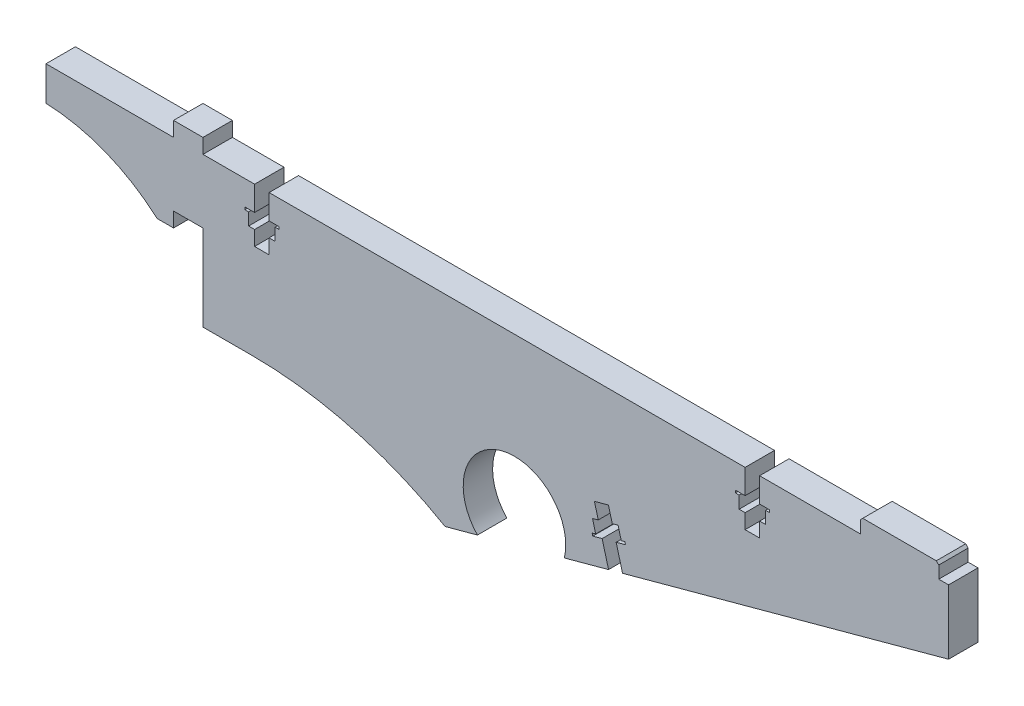
SolidWorks part; units mm, degrees
material "Oak"
ref_plane "Front Plane" through (0, 0, 0) normal (0, 0, 1) x (1, 0, 0)
ref_plane "Top Plane" through (0, 0, 0) normal (0, 1, 0) x (1, 0, 0)
ref_plane "Right Plane" through (0, 0, 0) normal (1, 0, 0) x (0, 0, -1)
sketch "Sketch1" plane through (0, 0, 0) normal (0, 0, 1) x (1, 0, 0)
  line L0 (127.02, 20) -> (127.02, 15)
  line L1 (16.5, -10.5) -> (16.5, 7)
  line L2 (16.5, 7) -> (10.5, 7)
  line L3 (10.5, 7) -> (10.5, 4)
  line L4 (10.5, 4) -> (7.1752, 4)
  line L5 (-15.5, 13) -> (-15.5, 20)
  line L6 (-15.5, 20) -> (10.5, 20)
  line L7 (166.5, 23) -> (166.5, 20)
  line L8 (72.4558, -19.231) -> (90.1661, -14.4192) construction
  line L9 (127.02, 15) -> (125.05, 15)
  line L10 (-18, 24.8801) -> (-18, -27.1715) construction
  line L11 (10.5, 20) -> (10.5, 23)
  line L12 (10.5, 23) -> (16.5, 23)
  line L13 (125.05, 15) -> (125.05, 14.5)
  line L14 (125.05, 14.5) -> (125.8, 14.5)
  line L15 (125.8, 14.5) -> (125.8, 12)
  line L16 (125.8, 12) -> (127.02, 12)
  line L17 (127.02, 12) -> (127.02, 9)
  line L18 (127.02, 9) -> (129.98, 9)
  line L19 (129.98, 12) -> (129.98, 9)
  line L20 (131.2, 12) -> (129.98, 12)
  line L21 (131.2, 14.5) -> (131.2, 12)
  line L22 (131.95, 14.5) -> (131.2, 14.5)
  line L23 (131.95, 15) -> (131.95, 14.5)
  line L24 (129.98, 15) -> (131.95, 15)
  line L25 (129.98, 20) -> (129.98, 15)
  line L26 (128.5, 20) -> (128.5, 9) construction
  line L27 (90.1661, -14.4192) -> (168.5, 6.8638)
  line L28 (80, -12) -> (81.311, -16.8251) construction
  line L29 (16.5, -10.5) -> (26.5, -10.5)
  line L30 (28.5, 20) -> (28.5, 9) construction
  line L31 (27.02, 20) -> (27.02, 15)
  line L32 (27.02, 15) -> (25.05, 15)
  line L33 (25.05, 15) -> (25.05, 14.5)
  line L34 (25.05, 14.5) -> (25.8, 14.5)
  line L35 (25.8, 14.5) -> (25.8, 12)
  line L36 (25.8, 12) -> (27.02, 12)
  line L37 (27.02, 12) -> (27.02, 9)
  line L38 (27.02, 9) -> (29.98, 9)
  line L39 (29.98, 12) -> (29.98, 9)
  line L40 (31.2, 12) -> (29.98, 12)
  line L41 (31.2, 14.5) -> (31.2, 12)
  line L42 (31.95, 14.5) -> (31.2, 14.5)
  line L43 (27.02, 20) -> (127.02, 20) construction
  line L44 (166.5, 20) -> (168.5, 20)
  line L45 (16.5, 23) -> (16.5, 20)
  line L46 (16.5, 20) -> (27.02, 20)
  line L47 (168.5, 20) -> (168.5, 6.8638)
  line L48 (65.8707, -21.0201) -> (64.5597, -16.1951) construction
  line L49 (64.5597, -16.1951) -> (80, -12) construction
  line L50 (65.8707, -21.0201) -> (72.4558, -19.231)
  line L51 (31.95, 15) -> (31.95, 14.5)
  line L52 (29.98, 15) -> (31.95, 15)
  line L53 (29.98, 20) -> (29.98, 15)
  line L54 (29.98, 20) -> (127.02, 20)
  line L55 (129.98, 20) -> (150.5, 20)
  line L56 (19.5, -3.7) -> (26.5, -3.7) construction
  line L57 (150.5, 20) -> (150.5, 23)
  line L58 (150.5, 23) -> (166.5, 23)
  line L59 (19.5, -2.7) -> (26.5, -2.7) construction
  line L60 (19.5, -4.7) -> (26.5, -4.7) construction
  circle A0 centre (0, 0) radius 6 construction
  circle A1 centre (80, -12) radius 6 construction
  arc A2 (90.1661, -14.4192) -> (72.4558, -19.231) centre (80, -12) ccw
  arc A3 (65.8707, -21.0201) -> (26.5, -10.5) centre (26.5, -89.4308) ccw
  arc A4 (19.5, -2.7) -> (19.5, -4.7) centre (19.5, -3.7) ccw construction
  arc A5 (26.5, -4.7) -> (26.5, -2.7) centre (26.5, -3.7) ccw construction
  arc A7 (7.1752, 4) -> (-15.5, 13) centre (-16.7107, -23.115) ccw
  point P56 (23, -3.7)
  dimension "D1" = 12
  dimension "D7" = 12
  dimension "D23" = 20.9
  dimension "D19" = 1
  dimension "D4" = 10.5
  dimension "D5" = 80
  dimension "D6" = 20
  dimension "D8" = 156
  dimension "D9" = 10.5
  dimension "D10" = 7
  dimension "D11" = 3
  dimension "D12" = 10
  dimension "D13" = 16.5
  dimension "D14" = 2
  dimension "D15" = 100
  dimension "D16" = 2
  dimension "D17" = 16
  dimension "D18" = 7
  dimension "D20" = 3.7
  dimension "D21" = 6.5
  dimension "D22" = 28.5
  dimension "D24" = 5
  dimension "D25" = 26
  dimension "D26" = 7
  dimension "D27" = 11
  dimension "D28" = 3
  dimension "D29" = 0.5
  dimension "D30" = 2.5
  dimension "D31" = 2.96
  dimension "D33" = 6.9
  dimension "D34" = 5.4
  dimension "D35" = 12
  dimension "D36" = 16
  dimension "D37" = 3
extrude "Boss-Extrude1" add sketch "Sketch1" along normal blind 6
chamfer "Chamfer1" [suppressed] distance 3 distance2 2
chamfer "Chamfer2" distance 0.5 angle 45 2 edges at (166.5, 23, 3) (150.5, 23, 3)
sketch "Sketch2" plane through (0, 0, 6) normal (0, 0, 1) x (1, 0, 0)
  line L0 (100.6113, -11.5813) -> (97.7272, -0.9661) construction
  line L1 (90.1661, -14.4192) -> (168.5, 6.8638) construction
  line L2 (102.0395, -11.1932) -> (99.1831, -11.9693)
  line L3 (96.299, -1.3541) -> (99.1554, -0.578)
  line L4 (99.1554, -0.578) -> (99.942, -3.4731)
  line L5 (99.942, -3.4731) -> (101.1193, -3.1532)
  line L6 (101.1193, -3.1532) -> (101.7748, -5.5658)
  line L7 (101.7748, -5.5658) -> (102.4985, -5.3691)
  line L8 (102.4985, -5.3691) -> (102.6296, -5.8516)
  line L9 (102.6296, -5.8516) -> (100.7285, -6.3681)
  line L10 (100.7285, -6.3681) -> (102.0395, -11.1932)
  line L11 (97.8721, -7.1442) -> (99.1831, -11.9693)
  line L12 (95.971, -7.6607) -> (97.8721, -7.1442)
  line L13 (95.8399, -7.1782) -> (95.971, -7.6607)
  line L14 (96.5637, -6.9816) -> (95.8399, -7.1782)
  line L15 (95.9082, -4.569) -> (96.5637, -6.9816)
  line L16 (97.0855, -4.2492) -> (95.9082, -4.569)
  line L17 (96.299, -1.3541) -> (97.0855, -4.2492)
  line L18 (80, -12) -> (99.3003, -6.7562) construction
  point P21 (80, -12)
  dimension "D1" = 2.96
  dimension "D2" = 6.9
  dimension "D3" = 5.4
  dimension "D4" = 0.5
  dimension "D5" = 2.5
  dimension "D6" = 3
  dimension "D7" = 11
  dimension "D8" = 20
extrude "Cut-Extrude1" cut sketch "Sketch2" against normal through all
equation "\"bed-plate-thickness\"=3"
equation "\"D1@Boss-Extrude1\"=\"y-cross-rib-thickness\""
equation "\"D37@Sketch1\" = \"bed-plate-thickness\""
equation "\"y-cross-rib-thickness\"=6"
equation "\"y-rib-thickness\"=6"
equation "\"x-plate-thickness\"=5"
equation "\"rod-diameter\"=12"
equation "\"t-nut-hole-diameter\"=3"
equation "\"D20@Sketch1\" = 9 - ( 11.6 / 2 ) + .5"
